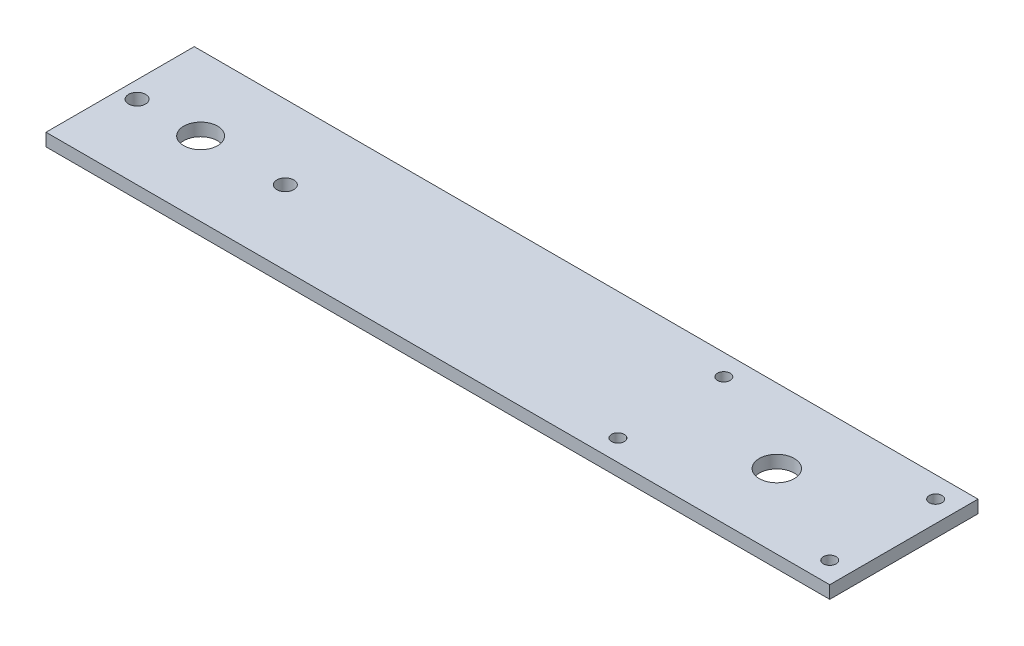
SolidWorks part; units mm, degrees
ref_plane "Front Plane" through (0, 0, 0) normal (0, 0, 1) x (1, 0, 0)
ref_plane "Top Plane" through (0, 0, 0) normal (0, 1, 0) x (1, 0, 0)
ref_plane "Right Plane" through (0, 0, 0) normal (1, 0, 0) x (0, 0, -1)
sketch "Sketch1" plane through (0, 0, 0) normal (0, 1, 0) x (1, 0, 0)
  line L1 (-92.5, 17.5) -> (92.5, 17.5)
  line L2 (-92.5, 17.5) -> (-92.5, -17.5)
  line L3 (-92.5, -17.5) -> (92.5, -17.5)
  line L4 (92.5, 17.5) -> (92.5, -17.5)
  line L5 (-92.5, 17.5) -> (92.5, -17.5) construction
  line L6 (-92.5, -17.5) -> (92.5, 17.5) construction
  circle A4 centre (62.5, 0) radius 4.125
  circle A8 centre (-88.5, 0) radius 2
  circle A9 centre (-53.5, 0) radius 2
  circle A11 centre (-73.5, 0) radius 4
  point P0 (0, 0)
  point P11 (0, 0)
  point P17 (92.5, 0)
  dimension "D3" = 30
  dimension "D4" = 17.5
  dimension "D5" = 15
  dimension "D6" = 8.25
  dimension "D8" = 8
  dimension "D1" = 35
  dimension "D2" = 185
extrude "Boss-Extrude1" add sketch "Sketch1" along normal blind 3
sketch "Sketch2" plane through (0, 3, 0) normal (0, 1, 0) x (1, 0, 0)
  line L0 (-92.5, 17.5) -> (-92.5, -17.5) construction
  line L1 (-92.5, -17.5) -> (92.5, -17.5) construction
  line L2 (-115.5, 6.5) -> (-115.5, -6.7467) construction
  circle A0 centre (-115.5, 6.5) radius 3
  circle A1 centre (-115.5, 6.5) radius 31 construction
  circle A2 centre (-27, 6.5) radius 57.5 construction
  circle A3 centre (-133, -0.5) radius 2
  circle A4 centre (-98, -0.5) radius 2
  dimension "D1" = 6
  dimension "D3" = 24
  dimension "D4" = 7
  dimension "D2" = 23
  dimension "D5" = 17.5
extrude "Cut-Extrude1" [suppressed] cut sketch "Sketch2" against normal through all contours A3 | A4
sketch "Sketch3" plane through (0, 3, 0) normal (0, 1, 0) x (1, 0, 0)
  line L0 (-92.5, -17.5) -> (92.5, -17.5) construction
  line L3 (92.5, 17.5) -> (92.5, -17.5) construction
  line L4 (-55, 0) -> (55, 0) construction
  circle A0 centre (72.5, -9.5) radius 1.5
  circle A3 centre (72.5, 9.5) radius 1.5
  dimension "D1" = 3
  dimension "D2" = 8
  dimension "D3" = 20
extrude "Cut-Extrude2" [suppressed] cut sketch "Sketch3" against normal through all
sketch "Sketch4" plane through (0, 3, 0) normal (0, 1, 0) x (1, 0, 0)
  line L0 (-92.5, 17.5) -> (92.5, 17.5) construction
  line L1 (62.5, 0) -> (41.5, 0) construction
  line L2 (92.5, 17.5) -> (92.5, -17.5) construction
  line L3 (-55, 0) -> (55, 0) construction
  circle A1 centre (52.5, 9.5) radius 1.5
  circle A2 centre (52.5, -9.5) radius 1.5
  dimension "D2" = 8
  dimension "D4" = 3
  dimension "D1" = 21
  dimension "D3" = 40
extrude "Cut-Extrude3" [suppressed] cut sketch "Sketch4" against normal through all
sketch "Sketch5" plane through (0, 3, 0) normal (0, 1, 0) x (1, 0, 0)
  line L0 (-64.8339, 7.0101) -> (-80.04, -19.3277) construction
  line L1 (-92.5, 17.5) -> (-92.5, -17.5) construction
  circle A0 centre (-73.5, 0) radius 4 construction
  circle A1 centre (-62.8075, 10.52) radius 1.5
  circle A2 centre (-77.2643, -14.52) radius 1.5
  dimension "D1" = 3
  dimension "D2" = 3
  dimension "D4" = 15
  dimension "D5" = 15
  dimension "D3" = 30
extrude "Cut-Extrude5" [suppressed] cut sketch "Sketch5" against normal through all
sketch "Sketch6" plane through (0, 3, 0) normal (0, 1, 0) x (1, 0, 0)
  line L0 (-92.5, 17.5) -> (92.5, 17.5) construction
  line L1 (92.5, 17.5) -> (92.5, -17.5) construction
  line L2 (-55, 0) -> (55, 0) construction
  line L3 (62.5, 0) -> (62.5, 14.7754) construction
  circle A0 centre (87.5, 12.5) radius 1.5
  circle A1 centre (87.5, -12.5) radius 1.5
  circle A2 centre (37.5, -12.5) radius 1.5
  circle A3 centre (37.5, 12.5) radius 1.5
  dimension "D3" = 3
  dimension "D1" = 5
  dimension "D2" = 5
extrude "Cut-Extrude6" cut sketch "Sketch6" against normal through all
sketch "Sketch7" plane through (0, 3, 0) normal (0, 1, 0) x (1, 0, 0)
  line L1 (62.5, 0) -> (87.5, 0)
  line L2 (62.5, 0) -> (62.5, 12.5)
  line L3 (62.5, 12.5) -> (87.5, 12.5)
  line L4 (87.5, 0) -> (87.5, 12.5)
